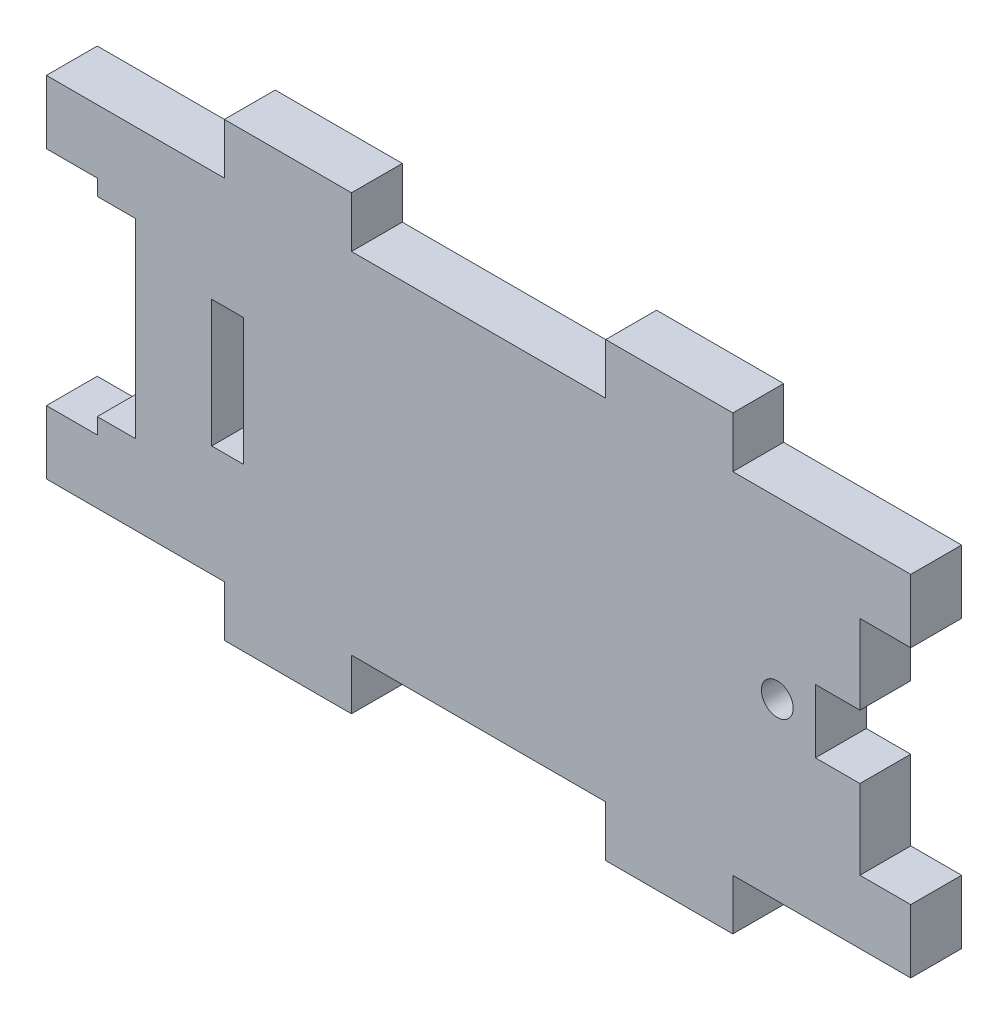
SolidWorks part; units mm, degrees
ref_plane "Front Plane" through (0, 0, 0) normal (0, 0, 1) x (1, 0, 0)
ref_plane "Top Plane" through (0, 0, 0) normal (0, 1, 0) x (1, 0, 0)
ref_plane "Right Plane" through (0, 0, 0) normal (1, 0, 0) x (0, 0, -1)
sketch "Sketch1" plane through (0, 0, 0) normal (0, 0, 1) x (1, 0, 0)
  line L1 (-60, 27.5) -> (60, 27.5)
  line L2 (-60, 27.5) -> (-60, -27.5)
  line L3 (-60, -27.5) -> (60, -27.5)
  line L4 (60, 27.5) -> (60, -27.5)
  line L5 (-42, -10) -> (-37, -10)
  line L6 (-42, -10) -> (-42, 10)
  line L7 (-42, 10) -> (-37, 10)
  line L8 (-37, -10) -> (-37, 10)
  circle A0 centre (47, 0) radius 2.5
  point P4 (0, 27.5)
  point P6 (60, 0)
  dimension "D6" = 13
  dimension "D1" = 55
  dimension "D2" = 120
  dimension "D3" = 20
  dimension "D4" = 17.5
  dimension "D5" = 18
extrude "Boss-Extrude1" add sketch "Sketch1" along normal blind 8
sketch "Sketch2" plane through (0, 0, 8) normal (0, 0, 1) x (1, 0, 0)
  line L0 (-60, 27.5) -> (-60, -27.5) construction
  line L1 (-92.7508, 15) -> (-54, 15)
  line L2 (-92.7508, 15) -> (-92.7508, -15)
  line L3 (-92.7508, -15) -> (-54, -15)
  line L4 (-54, 15) -> (-54, -15)
  point P4 (-54, 0)
  point P7 (-60, 0)
  dimension "D1" = 30
  dimension "D2" = 6
extrude "Cut-Extrude1" cut sketch "Sketch2" against normal up to next
sketch "Sketch4" plane through (60, 0, 0) normal (1, 0, 0) x (0, 0, -1)
  line L1 (-8, 27.5) -> (0, 27.5)
  line L2 (-8, 27.5) -> (-8, 17.5)
  line L3 (-8, 17.5) -> (0, 17.5)
  line L4 (0, 27.5) -> (0, 17.5)
  line L5 (-8, 27.5) -> (0, 27.5) construction
  line L6 (0, -27.5) -> (0, 27.5) construction
  line L7 (-23.1797, 0) -> (12.6777, 0) construction
  line L8 (-8, -27.5) -> (-8, -17.5)
  line L9 (-8, -27.5) -> (0, -27.5)
  line L10 (0, -27.5) -> (0, -17.5)
  line L11 (-8, -17.5) -> (0, -17.5)
  dimension "D1" = 10
extrude "Boss-Extrude3" add sketch "Sketch4" along normal blind 8
sketch "Sketch6" plane through (0, -27.5, 0) normal (0, -1, 0) x (1, 0, 0)
  line L0 (0, 25.2996) -> (0, -15.5638) construction
  line L1 (-40, 8) -> (-20, 8)
  line L2 (-40, 8) -> (-40, 0)
  line L3 (-40, 0) -> (-20, 0)
  line L4 (-20, 8) -> (-20, 0)
  line L5 (20, 8) -> (20, 0)
  line L6 (40, 0) -> (20, 0)
  line L7 (40, 8) -> (40, 0)
  line L8 (40, 8) -> (20, 8)
  line L9 (-60, 8) -> (68, 8) construction
  line L10 (-60, 0) -> (68, 0) construction
  dimension "D1" = 20
  dimension "D2" = 40
extrude "Boss-Extrude4" add sketch "Sketch6" along normal blind 8
ref_plane "Plane1" through (0, 0, 0) normal (0, -1, 0) x (-1, 0, 0)
mirror "Mirror2" about plane through (0, 0, 0) normal (0, -1, 0) of "Boss-Extrude4"
ref_plane "Plane2" through (0, 0, 0) normal (-1, 0, 0) x (0, 0, 1)
mirror "Mirror3" about plane through (0, 0, 0) normal (-1, 0, 0) of "Boss-Extrude3"
sketch "Sketch7" plane through (60, 0, 0) normal (1, 0, 0) x (0, 0, -1)
  line L0 (-8, -17.5) -> (-8, 17.5) construction
  line L1 (-8, 5) -> (0, 5)
  line L2 (-8, 5) -> (-8, -5)
  line L3 (-8, -5) -> (0, -5)
  line L4 (0, 5) -> (0, -5)
  line L5 (0, -17.5) -> (0, 17.5) construction
  line L6 (-8, 17.5) -> (0, -17.5) construction
  line L7 (0, 17.5) -> (-8, -17.5) construction
  line L8 (-8, 5) -> (0, -5) construction
  point P16 (-16.1988, -1.3276)
  point P17 (-4, 0)
  dimension "D1" = 10
extrude "Cut-Extrude2" cut sketch "Sketch7" against normal blind 7
